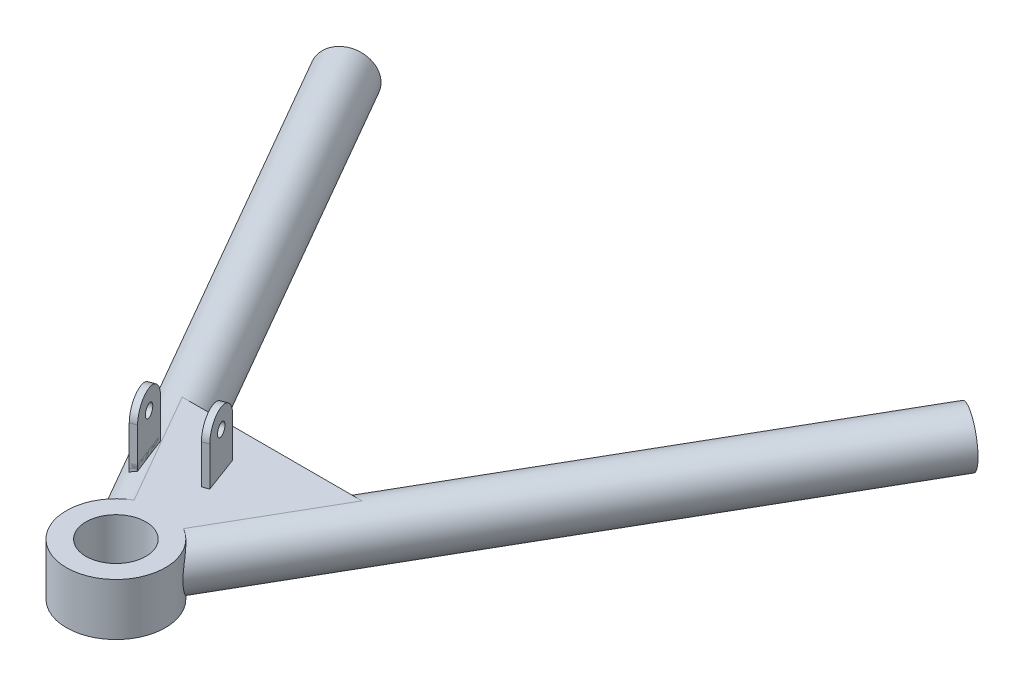
SolidWorks part; units mm, degrees
note: The reader was unsure of these and kept them because the rebuilt part matched: shared geometry of "Sketch14<2>".
material "AISI 4130 Steel, annealed at 865C"
ref_plane "Front Plane" through (0, 0, 0) normal (0, 0, 1) x (1, 0, 0)
ref_plane "Top Plane" through (0, 0, 0) normal (0, 1, 0) x (1, 0, 0)
ref_plane "Right Plane" through (0, 0, 0) normal (1, 0, 0) x (0, 0, -1)
sketch "Sketch1" plane through (0, 0, 0) normal (0, 1, 0) x (1, 0, 0)
  circle A0 centre (0, 0) radius 11.5062
  circle A1 centre (0, 0) radius 19.0062
  dimension "D3" = 23.0124
  dimension "D1" = 38.0124
extrude "Boss-Extrude1" add sketch "Sketch1" along normal mid plane 20
sketch "Sketch3" plane through (0, 0, 0) normal (0, 1, 0) x (1, 0, 0)
  line L0 (-19.0062, 0) -> (19.0062, 0) construction
  line L1 (0, 0) -> (-135.5, 235.3859) construction
  line L2 (0, 0) -> (119.6742, 207.8939) construction
  line L3 (-9.4821, 16.472) -> (-135.5, 235.3859) construction
  line L4 (9.4821, 16.472) -> (119.6742, 207.8939) construction
  line L6 (119.6742, 207.8939) -> (142.2716, 194.8857) construction
  line L7 (-119.6742, 207.8939) -> (-147.9725, 191.604) construction
  line L8 (0, 0) -> (135.5, 235.3859) construction
  line L9 (-135.5, 235.3859) -> (135.5, 235.3859) construction
  circle A0 centre (0, 0) radius 19.0062 construction
  circle A1 centre (0, 0) radius 19.0062 construction
  dimension "D1" = 60.073
  dimension "D2" = 60.073
  dimension "D3" = 271.6004
  dimension "D5" = 31.7217
  dimension "D4" = 271.6004
  dimension "D6" = 31.7217
ref_plane "tube1plane" through (119.6742, 0, -207.8939) normal (0.4989, 0, -0.8667) x (0.8667, 0, 0.4989)
ref_plane "tube2plane" through (-119.6742, 0, -207.8939) normal (-0.4989, 0, -0.8667) x (-0.8667, 0, 0.4989)
sketch "Sketch5" plane through (119.6742, 0, -207.8939) normal (0.4989, 0, -0.8667) x (0.8667, 0, 0.4989)
  circle A0 centre (0, 0) radius 10
  circle A1 centre (0, 0) radius 7
  dimension "D1" = 20
  dimension "D2" = 14
extrude "Boss-Extrude2" add sketch "Sketch5" against normal up to next
sketch "Sketch6" plane through (-119.6742, 0, -207.8939) normal (-0.4989, 0, -0.8667) x (-0.8667, 0, 0.4989)
  circle A0 centre (0, 0) radius 10
  circle A1 centre (0, 0) radius 7
  dimension "D1" = 20
  dimension "D2" = 14
extrude "Boss-Extrude3" add sketch "Sketch6" against normal up to surface (223.7159 mm away)
sketch "Sketch13" plane through (0, 10, 0) normal (0, 1, 0) x (1, 0, 0)
  line L0 (9.4821, 16.472) -> (34.539, 60)
  line L1 (-9.4821, 16.472) -> (-34.539, 60)
  line L2 (0, 0) -> (-135.5, 235.3859) construction
  line L3 (0, 0) -> (119.6742, 207.8939) construction
  line L4 (34.539, 60) -> (-34.539, 60)
  arc A1 (9.4821, 16.472) -> (0, 19.0062) centre (0, 0) ccw construction
  arc A2 (9.4821, 16.472) -> (-9.4821, 16.472) centre (0, 0) ccw construction
  arc A3 (9.4821, 16.472) -> (-9.4821, 16.472) centre (0, 0) ccw
  dimension "D1" = 60
extrude "Boss-Extrude7" add sketch "Sketch13" against normal blind 7.5
sketch3d "3DSketch1"
  line L0 (0, 0, 0) -> (0, 0, -37.5) construction
  line L1 (0, 0, -37.5) -> (-12.5, 0, -37.5) construction
  line L2 (-12.5, 0, -37.5) -> (-12.5, 25, -37.5) construction
  line L3 (-12.5, 0, -37.5) -> (1.4912, 0, 0) construction
  line L4 (1.4912, 0, 0) -> (1.4912, 0, -34.2898) construction
  line L5 (0, 0, 0) -> (1.4912, 0, 0) construction
  line L6 (-19.0062, 0, 0) -> (19.0062, 0, 0) construction
  dimension "D1" = 25
  dimension "D2" = 37.5
  dimension "D3" = 12.5
  dimension "D4" = 20.46
ref_plane "Mount mid plane" through (1.309, 0, -0.4884) normal (-0.9369, 0, 0.3496) x (0.3496, 0, 0.9369)
sketch "Sketch14" plane through (1.309, 0, -0.4884) normal (-0.9369, 0, 0.3496) x (0.3496, 0, 0.9369)
  line L0 (-47.0038, 10) -> (-47.0038, 25)
  line L1 (-68.2883, 10) -> (-18.7474, 10) construction
  line L2 (-39.5038, 0) -> (-39.5038, 25) construction
  line L3 (-39.5038, 30) -> (-39.5038, 0) construction
  line L4 (-32.0038, 10) -> (-32.0038, 25)
  line L5 (-47.0038, 10) -> (-32.0038, 10)
  circle A0 centre (-39.5038, 25) radius 2.413
  arc A1 (-47.0038, 25) -> (-32.0038, 25) centre (-39.5038, 25) cw
  dimension "D1" = 4.826
  dimension "D2" = 7.5
extrude "Boss-Extrude8" add sketch "Sketch14" along normal mid plane 24.05
extrude "Cut-Extrude1" cut sketch "Sketch14<2>" against normal mid plane 19.05
sketch "Sketch14<2>" plane through (1.309, 0, -0.4884) normal (-0.9369, 0, 0.3496) x (0.3496, 0, 0.9369) same geometry as "Sketch14"
sketch "Sketch15" plane through (-9.9574, 0, 3.7151) normal (-0.9369, 0, 0.3496) x (0.3496, 0, 0.9369)
  line L0 (-39.5038, 0) -> (-39.5038, 25) construction
  line L1 (-32.0038, 8) -> (-47.0038, 8)
  line L2 (-32.0038, 8) -> (-32.0038, 12)
  line L3 (-32.0038, 12) -> (-47.0038, 12)
  line L4 (-47.0038, 8) -> (-47.0038, 12)
  line L5 (-32.0038, 8) -> (-47.0038, 12) construction
  line L6 (-32.0038, 12) -> (-47.0038, 8) construction
  line L7 (-47.0038, 25) -> (-47.0038, 10) construction
  line L8 (-12.1182, 0) -> (-152.9451, 0) construction
  point P0 (-39.5038, 10)
  dimension "D1" = 4
  dimension "D2" = 8
extrude "Boss-Extrude9" add sketch "Sketch15" against normal up to surface (2.5 mm away)
equation "\"CA_ID\"= 14"
equation "\"D2@Sketch5\"=\"CA_ID\""
equation "\"D2@Sketch6\"=\"CA_ID\""
equation "\"tube_end_to_ball_center\" = 31.721675mm"
equation "\"D6@Sketch3\"=\"tube_end_to_ball_center\""
equation "\"D5@Sketch3\"=\"tube_end_to_ball_center\""
